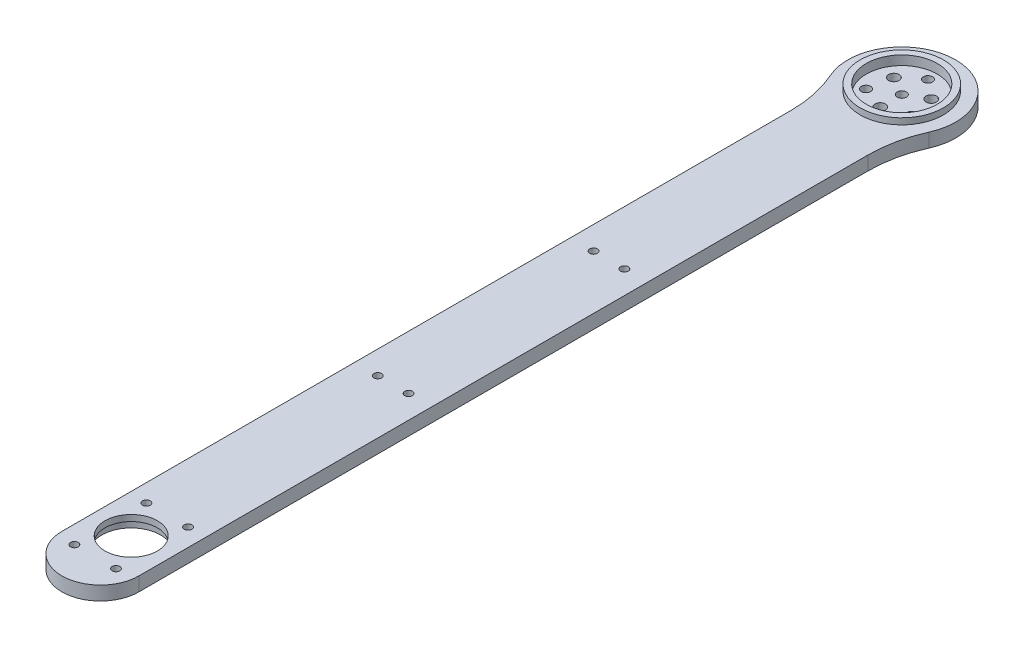
SolidWorks part; units mm, degrees
other "마크업1"
sketch "스케치14" plane through (-17.5, 12, -17.5) normal (-0.0092, 0.8478, -0.5302) x (0.9606, -0.1397, -0.2401)
sketch "스케치15" plane through (-17.5, 12, -17.5) normal (-0.0092, 0.8478, -0.5302) x (0.9606, -0.1397, -0.2401)
sketch "스케치16" plane through (-17.5, 12, -17.5) normal (-0.0092, 0.8478, -0.5302) x (0.9606, -0.1397, -0.2401)
sketch "스케치17" plane through (-17.5, 12, -17.5) normal (-0.0092, 0.8478, -0.5302) x (0.9606, -0.1397, -0.2401)
sketch "스케치18" plane through (-17.5, 11, -17.5) normal (-0.0092, 0.8478, -0.5302) x (0.9606, -0.1397, -0.2401)
sketch "스케치19" plane through (-17.5, 11, -17.5) normal (-0.0092, 0.8478, -0.5302) x (0.9606, -0.1397, -0.2401)
sketch "스케치20" plane through (-17.5, 11, -17.5) normal (-0.0092, 0.8478, -0.5302) x (0.9606, -0.1397, -0.2401)
sketch "스케치21" plane through (-17.5, 11, -17.5) normal (-0.0092, 0.8478, -0.5302) x (0.9606, -0.1397, -0.2401)
sketch "스케치22" plane through (-17.5, 11, -17.5) normal (-0.0092, 0.8478, -0.5302) x (0.9606, -0.1397, -0.2401)
sketch "스케치24" plane through (-17.5, 11, -17.5) normal (-0.0092, 0.8478, -0.5302) x (0.9606, -0.1397, -0.2401)
sketch "스케치25" plane through (-17.5, 11, -17.5) normal (-0.0092, 0.8478, -0.5302) x (0.9606, -0.1397, -0.2401)
sketch "스케치27" plane through (-17.5, 11, -17.5) normal (-0.0092, 0.8478, -0.5302) x (0.9606, -0.1397, -0.2401)
sketch "스케치35" plane through (-17.5, 11, -17.5) normal (-0.0092, 0.8478, -0.5302) x (0.9606, -0.1397, -0.2401)
sketch "스케치43" plane through (-17.5, 11, -17.5) normal (-0.0092, 0.8478, -0.5302) x (0.9606, -0.1397, -0.2401)
sketch "스케치45" plane through (-17.5, 11, -17.5) normal (-0.0092, 0.8478, -0.5302) x (0.9606, -0.1397, -0.2401)
material "7075-T6 (SN)"
ref_plane "정면" through (0, 0, 0) normal (0, 0, 1) x (1, 0, 0)
ref_plane "윗면" through (0, 0, 0) normal (0, 1, 0) x (1, 0, 0)
ref_plane "우측면" through (0, 0, 0) normal (1, 0, 0) x (0, 0, -1)
sketch "스케치1" plane through (0, 0, 0) normal (0, 1, 0) x (1, 0, 0)
  line L0 (-12.5, -260) -> (-12.5, -12.2474)
  line L1 (0, 0) -> (0, -260) construction
  line L2 (12.5, -260) -> (12.5, -12.2474)
  arc A1 (12.5, -12.2474) -> (-12.5, -12.2474) centre (0, 0) ccw
  arc A2 (-12.5, -260) -> (12.5, -260) centre (0, -260) ccw
  dimension "D2" = 35
  dimension "D3" = 25
  dimension "D4" = 260
extrude "보스-돌출1" add sketch "스케치1" along normal blind 9
sketch "스케치3" plane through (0, 9, 0) normal (0, 1, 0) x (1, 0, 0)
  circle A0 centre (0, 0) radius 13.5
  dimension "D1" = 27
extrude "보스-돌출2" add sketch "스케치3" along normal blind 2 contours A0 region at (0, 9, 0)
sketch "스케치4" plane through (0, 0, 0) normal (0, -1, 0) x (1, 0, 0)
  circle A0 centre (0, 0) radius 13.5
  dimension "D1" = 27
extrude "보스-돌출3" add sketch "스케치4" along normal blind 3 contours A0 region at (0, 0, 0)
sketch "스케치5" plane through (0, 9, 0) normal (0, 1, 0) x (1, 0, 0)
  circle A0 centre (0, -250) radius 9.5
  dimension "D1" = 19
  dimension "D2" = 250
extrude "컷-돌출2" cut sketch "스케치5" against normal through all
sketch "스케치7" plane through (0, -3, 0) normal (0, -1, 0) x (1, 0, 0)
  circle A0 centre (0, 0) radius 7
  point P3 (0, 7)
  dimension "D1" = 14
hole_wizard "M3 육각 소켓 머리 캡 나사용 카운터보어1" positions "스케치8" profile "스케치10" counterbore size "M3" standard "ISO" end condition through all
sketch "스케치8" plane through (0, -3, 0) normal (0, -1, 0) x (-1, 0, 0)
  point P0 (0, -7)
sketch "스케치10" plane through (0, -3, 7) normal (1, 0, 0) x (0, 0, -1)
  line L0 (0, 0) -> (0, 14)
  line L1 (0, 14) -> (1.7, 14)
  line L3 (1.7, 14) -> (1.7, 3.4)
  line L4 (1.7, 3.4) -> (3.25, 3.4)
  line L5 (3.25, 3.4) -> (3.25, 0)
  line L7 (3.25, 0) -> (0, 0)
  line L11 (0, -6.35) -> (0, 107.95) construction
  dimension "관통 구멍 지름" = 3.4
  dimension "관통 구멍 깊이" = 14
  dimension "카운터보어 지름" = 6.5
  dimension "카운터보어 깊이" = 3.4
pattern_circular "원형 패턴1" count 3 over 360 about axis through (0, 9, 0) along (0, -1, 0) of "M3 육각 소켓 머리 캡 나사용 카운터보어1"
sketch "스케치11" plane through (0, -3, 0) normal (0, -1, 0) x (1, 0, 0)
  circle A0 centre (0, 0) radius 12.5
  circle A1 centre (6.0622, -3.5) radius 3.25 construction
  circle A2 centre (0, 0) radius 13.5
  circle A3 centre (0, 0) radius 13.5
  circle A4 centre (-6.0622, -3.5) radius 3.25 construction
  circle A5 centre (0, 7) radius 3.25 construction
  circle A6 centre (6.0622, -3.5) radius 3.25
  circle A7 centre (-6.0622, -3.5) radius 3.25
  circle A8 centre (0, 7) radius 3.25
  circle M1 centre (6.0622, -3.5) radius 3.25
  circle M2 centre (-6.0622, -3.5) radius 3.25
  circle M3 centre (0, 7) radius 3.25
  dimension "D1" = 25
  dimension "D2" = 0
extrude "보스-돌출4" add sketch "스케치11" along normal blind 7 contours A0 M1 M3 M2 region at (0, -3, 0)
sketch "스케치13" plane through (0, 11, 0) normal (0, 1, 0) x (1, 0, 0)
  circle A0 centre (0, 0) radius 11.5
  dimension "D1" = 23
extrude "컷-돌출3" cut sketch "스케치13" against normal blind 3
fillet "필렛1" radius 40 2 edges at (12.5, 4.5, 12.2474) (-12.5, 4.5, 12.2474)
sketch "스케치23" plane through (0, -10, 0) normal (0, -1, 0) x (1, 0, 0)
  circle A0 centre (0, 0) radius 11
  dimension "D1" = 22
extrude "컷-돌출4" [suppressed] cut sketch "스케치23" against normal blind 5
sketch "스케치26" plane through (0, 0, 0) normal (0, 0, 1) x (1, 0, 0)
  line L1 (-32.4505, -20.3988) -> (32.6856, -20.3988)
  line L2 (-32.4505, -20.3988) -> (-32.4505, 4.5)
  line L3 (-32.4505, 4.5) -> (32.6856, 4.5)
  line L4 (32.6856, -20.3988) -> (32.6856, 4.5)
  line L6 (-33.8554, 0) -> (36.1825, 0) construction
  line L7 (-13.5, 0) -> (13.5, 0) construction
  dimension "D1" = 4.5
extrude "컷-돌출5" cut sketch "스케치26" against normal mid plane 2222
sketch "스케치28" plane through (0, 9, 0) normal (0, 1, 0) x (1, 0, 0)
  circle A0 centre (0, -250) radius 8.5
  circle A1 centre (0, -250) radius 9.5 construction
  circle A2 centre (0, -250) radius 9.5
  dimension "D1" = 17
extrude "보스-돌출5" add sketch "스케치28" against normal blind 2
sketch "스케치29" plane through (0, 4.5, 0) normal (0, -1, 0) x (1, 0, 0)
  line L0 (-21.0693, 250) -> (32.5304, 250) construction
  line L1 (0, 250) -> (-18.0954, 281.3422) construction
  circle A0 centre (0, 250) radius 13.5 construction
  circle A1 centre (0, 250) radius 9.5 construction
  point P6 (-6.75, 261.6913)
  dimension "D1" = 27
  dimension "D2" = 60
sketch "스케치32" plane through (0, 4.5, 0) normal (0, -1, 0) x (1, 0, 0)
  line L0 (-38.5353, 25) -> (53.5715, 25) construction
  line L1 (-38.5353, 0) -> (53.5715, 0) construction
  line L2 (-5, 54.8561) -> (-5, -31.7681) construction
  line L3 (0, 72.6196) -> (0, -53.9176) construction
  dimension "D1" = 25
  dimension "D2" = 5
hole_wizard "M3 탭을 위한 탭 드릴2" positions "스케치33" profile "스케치34" hole size "M3" standard "ISO" end condition through all
sketch "스케치33" plane through (0, 4.5, 0) normal (0, -1, 0) x (-1, 0, 0)
  line L0 (38.5353, -25) -> (-53.5715, -25) construction
  line L1 (5, -54.8561) -> (5, 31.7681) construction
  point P0 (5, -25)
sketch "스케치34" plane through (-5, 4.5, 25) normal (1, 0, 0) x (0, 0, -1)
  line L0 (0, 0) -> (0, 6.5)
  line L1 (0, 6.5) -> (1.25, 6.5)
  line L2 (1.25, 6.5) -> (1.25, 0)
  line L5 (1.25, 0) -> (0, 0)
  line L11 (0, -6.35) -> (0, 107.95) construction
  dimension "관통 구멍 지름" = 2.5
  dimension "관통 구멍 깊이" = 6.5
pattern_linear "선형 패턴1" count 3 spacing 70 along (0, 0, 1) count 2 spacing 10 along (1, 0, 0) of "M3 탭을 위한 탭 드릴2"
sketch "스케치36" plane through (0, 8, 0) normal (0, 1, 0) x (1, 0, 0)
  circle A0 centre (0, 0) radius 8.5 construction
  circle A1 centre (0, 0) radius 11.5 construction
  point P4 (0, 8.5)
  dimension "D1" = 17
hole_wizard "M3 탭을 위한 탭 드릴3" positions "스케치41" profile "스케치42" hole size "M3" standard "ISO" end condition through all
sketch "스케치41" plane through (0, 4.5, 0) normal (0, -1, 0) x (-1, 0, 0)
  point P0 (6.75, -261.6913)
sketch "스케치42" plane through (-6.75, 4.5, 261.6913) normal (1, 0, 0) x (0, 0, -1)
  line L0 (0, 0) -> (0, 6.5)
  line L1 (0, 6.5) -> (1.25, 6.5)
  line L2 (1.25, 6.5) -> (1.25, 0)
  line L5 (1.25, 0) -> (0, 0)
  line L11 (0, -6.35) -> (0, 107.95) construction
  dimension "관통 구멍 지름" = 2.5
  dimension "관통 구멍 깊이" = 6.5
pattern_circular "원형 패턴4" count 6 over 360 about axis through (0, -3, 250) along (0, 1, 0) skipping 2, 5 of "M3 탭을 위한 탭 드릴3"
sketch "스케치44" plane through (0, 4.5, 0) normal (0, -1, 0) x (1, 0, 0)
  circle A0 centre (5, 25) radius 1.25
  circle A1 centre (5, 25) radius 1.25 construction
  circle A2 centre (-5, 25) radius 1.25
  circle A3 centre (-5, 25) radius 1.25 construction
extrude "보스-돌출6" add sketch "스케치44" against normal blind 4.5
hole_wizard "Ø3.0mm 맞춤핀 구멍2" positions "스케치47" profile "스케치48" hole size "Ø3.0" standard "ISO"
sketch "스케치47" plane through (0, 4.5, 0) normal (0, -1, 0) x (-1, 0, 0)
  point P0 (0, 0)
sketch "스케치48" plane through (0, 4.5, 0) normal (1, 0, 0) x (0, 0, -1)
  line L0 (0, 0) -> (0, 5.9013)
  line L1 (0, 5.9013) -> (1.5, 5)
  line L2 (1.5, 5) -> (1.5, 0)
  line L5 (1.5, 0) -> (0, 0)
  line L10 (0, 5.9013) -> (-1.5, 5) construction
  line L11 (0, -6.35) -> (0, 107.95) construction
  dimension "구멍 지름" = 3
  dimension "구멍 깊이" = 5
  dimension "드릴 각도" = 118
hole_wizard "Ø3.0mm 맞춤핀 구멍3" positions "스케치49" profile "스케치50" hole size "Ø3.0" standard "ISO"
sketch "스케치49" plane through (0, 8, 0) normal (0, 1, 0) x (1, 0, 0)
  point P0 (0, 8.5)
sketch "스케치50" plane through (0, 8, -8.5) normal (1, 0, 0) x (0, 0, 1)
  line L0 (0, 0) -> (0, 5.9013)
  line L1 (0, 5.9013) -> (1.5, 5)
  line L2 (1.5, 5) -> (1.5, 0)
  line L5 (1.5, 0) -> (0, 0)
  line L10 (0, 5.9013) -> (-1.5, 5) construction
  line L11 (0, -6.35) -> (0, 107.95) construction
  dimension "구멍 지름" = 3
  dimension "구멍 깊이" = 5
  dimension "드릴 각도" = 118
pattern_circular "원형 패턴5" count 3 over 360 about axis through (0, 11, 0) along (0, -1, 0) of "Ø3.0mm 맞춤핀 구멍3"
